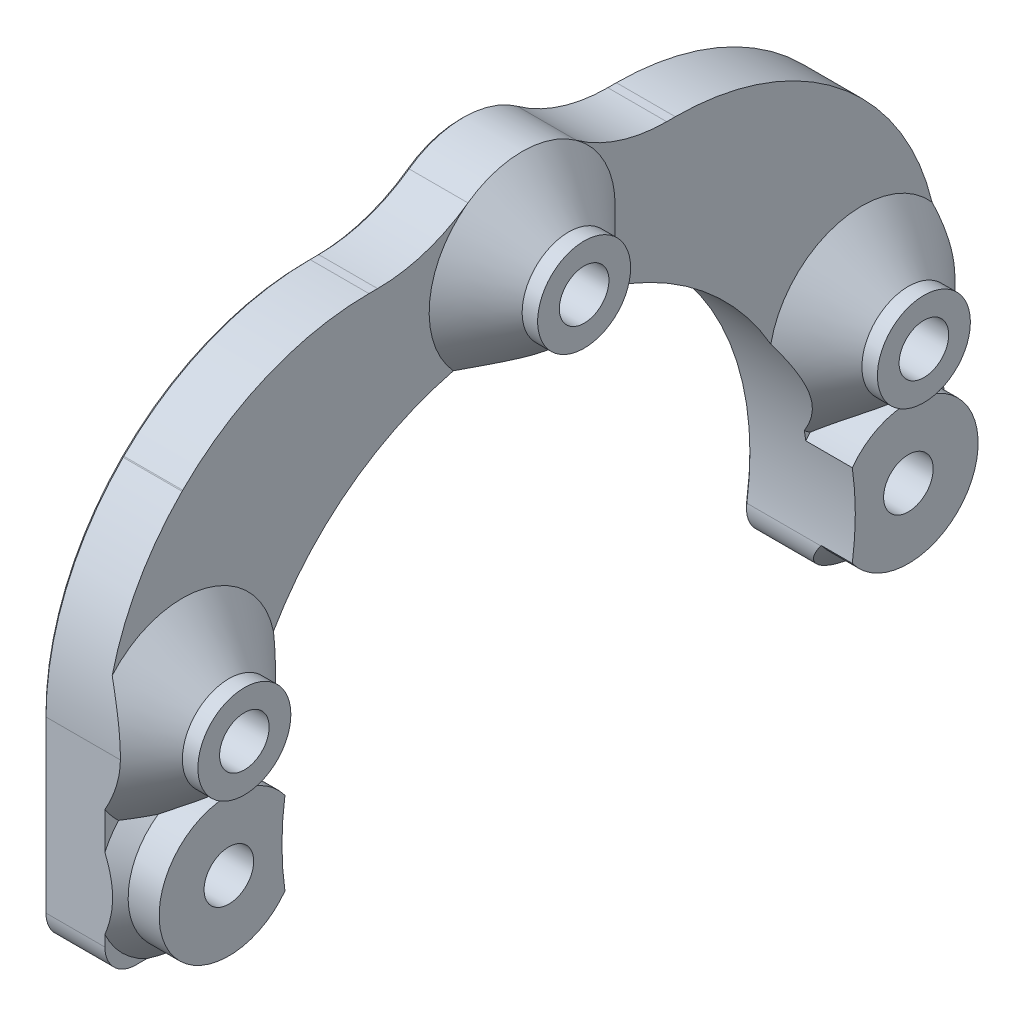
SolidWorks part; units mm, degrees
ref_plane "前视基准面" through (0, 0, 0) normal (0, 0, 1) x (1, 0, 0)
ref_plane "上视基准面" through (0, 0, 0) normal (0, 1, 0) x (1, 0, 0)
ref_plane "右视基准面" through (0, 0, 0) normal (1, 0, 0) x (0, 0, -1)
other "Configuration Table"
sketch "草图1" plane through (0, 0, 0) normal (1, 0, 0) x (0, 0, -1)
  line L1 (0, 0) -> (53.85, 0)
  line L2 (0, 0) -> (0, -30)
  line L3 (0, -30) -> (53.85, -30)
  line L4 (53.85, 0) -> (53.85, -30)
  circle A0 centre (5, -25) radius 1.6
  circle A1 centre (48.85, -25) radius 1.6
  dimension "D3" = 3.2
  dimension "D4" = 3.2
  dimension "D1" = 43.85
  dimension "D2" = 53.85
  dimension "D5" = 5
  dimension "D6" = 5
  dimension "D7" = 5
  dimension "D8" = 30
extrude "凸台-拉伸1" add sketch "草图1" along normal blind 4
sketch "草图7" plane through (4, 0, 0) normal (1, 0, 0) x (0, 0, -1)
  circle A0 centre (5, -25) radius 1.6
  circle A1 centre (48.85, -25) radius 1.6
  circle A2 centre (5, -25) radius 4.5
  circle A3 centre (48.85, -25) radius 4.5
  dimension "D1" = 9
  dimension "D2" = 9
extrude "凸台-拉伸3" add sketch "草图7" along normal blind 3
sketch "草图2" plane through (4, 0, 0) normal (1, 0, 0) x (0, 0, -1)
  line L0 (0, -30) -> (53.85, -30) construction
  circle A0 centre (26.925, -25) radius 18.5
  point P4 (26.925, -30)
  dimension "D3" = 37
  dimension "D1" = 5
  dimension "D2" = 0
extrude "切除-拉伸1" cut sketch "草图2" against normal blind 4 and the other way through all
chamfer "倒角1" distance 10 angle 45 2 edges at (2, 0, -53.85) (2, 0, 0)
sketch "草图3" plane through (4, 0, 0) normal (1, 0, 0) x (0, 0, -1)
  line L0 (53.85, -30) -> (53.85, -10) construction
  line L1 (0, -10) -> (0, -30) construction
  line L3 (0, -30) -> (9.1135, -30) construction
  line L4 (44.7365, -30) -> (53.85, -30) construction
  line L5 (43.85, 0) -> (10, 0) construction
  circle A0 centre (5, -17) radius 3
  circle A1 centre (48.85, -17) radius 3
  circle A2 centre (26.925, -3) radius 3
  point P16 (26.925, 0)
  dimension "D1" = 6
  dimension "D2" = 6
  dimension "D5" = 13
  dimension "D6" = 13
  dimension "D7" = 0
  dimension "D8" = 3
  dimension "D9" = 6
  dimension "D3" = 5
  dimension "D4" = 5
extrude "凸台-拉伸2" add sketch "草图3" along normal blind 4
sketch "草图4" plane through (8, 0, 0) normal (1, 0, 0) x (0, 0, -1)
  circle A0 centre (5, -17) radius 1.6
  circle A1 centre (48.85, -17) radius 1.6
  circle A2 centre (26.925, -3) radius 1.6
  dimension "D1" = 3.2
  dimension "D2" = 3.2
  dimension "D3" = 3.2
extrude "切除-拉伸2" cut sketch "草图4" against normal through all
sketch "草图8" plane through (0, 0, 0) normal (-1, 0, 0) x (0, 0, 1)
  circle A0 centre (-26.925, -3) radius 1.6
  arc A1 (-22.4888, -7.0398) -> (-31.3612, -7.0398) centre (-26.925, -3) ccw
  arc A3 (-22.4888, -7.0398) -> (-31.3612, -7.0398) centre (-26.925, -25) ccw
  dimension "D1" = 6
extrude "凸台-拉伸4" add sketch "草图8" against normal blind 4
fillet "圆角3" radius 10 2 edges at (2, 0, -21.7288) (2, 0, -32.1212)
chamfer "倒角3" distance 3 angle 45 3 edges at (4, -17, -51.85) (4, -17, -8) (4, -3, -29.925)
chamfer "倒角4" distance 1 angle 45 2 edges at (4, -28.4839, -51.6983) (4, -28.4839, -2.1517)
fillet "圆角1" radius 2 4 edges at (2, -30, -44.7365) (2, -30, -9.1135) (2, -30, -53.85) (2, -30, 0)
fillet "圆角2" radius 17 4 edges at (2, -10, -53.85) (2, 0, -43.85) (2, -10, 0) (2, 0, -10)
chamfer "倒角5" distance 0.2 angle 45 25 edges at (0, -25, -50.45) (0, -25, -6.6) (0, -1.294, -43.314) (0, 0, -17.3196) (0, 0, -36.5304) (0, -1.294, -10.536) (0, -5, -5) (0, -10.536, -1.294) (0, -22.5208, 0) (0, -29.4142, -0.5858) (0, -30, -4.3229) (0, -29.3066, -8.1599) (0, -6.5, -26.925) (0, -29.3066, -45.6901) (0, -30, -49.5271) (0, -29.4142, -53.2642) (0, -22.5208, -53.85) (0, -10.536, -52.556) (0, -5, -48.85) (0, -3, -28.525) (0, -17, -50.45) (0, -17, -6.6) (0, 3, -26.925) (0, 0.4803, -33.1905) (0, 0.4803, -20.6595)
equation "\"D2@草图1\"=\"D1@草图1\"+10"
